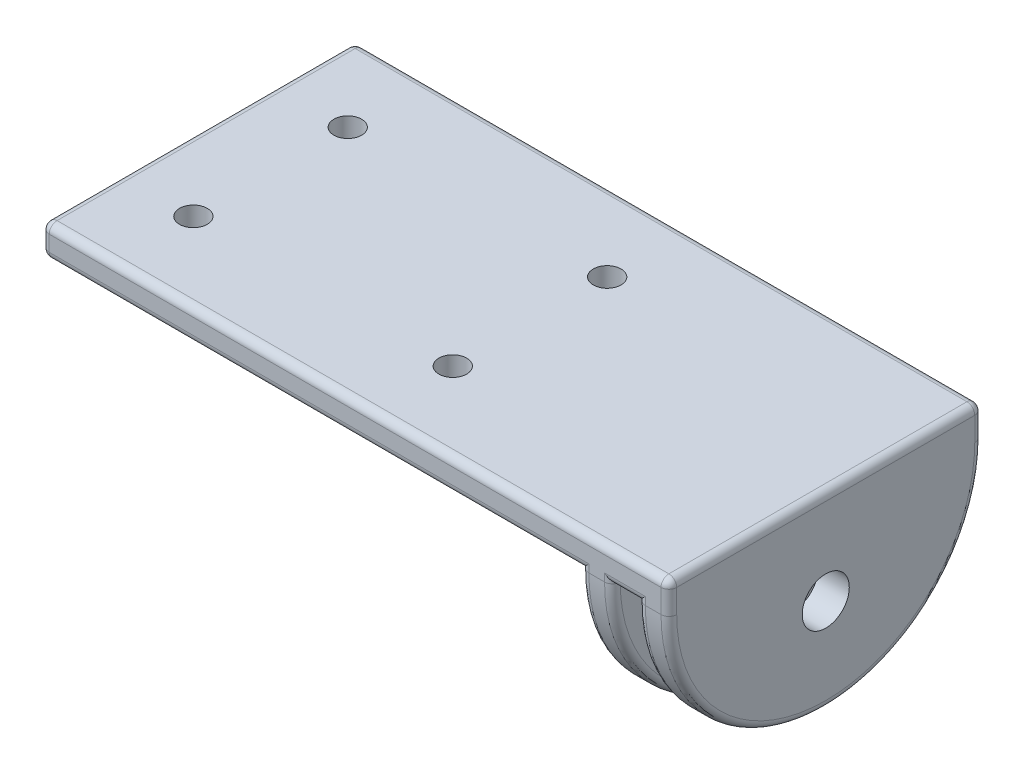
SolidWorks part; units mm, degrees
ref_plane "Front Plane" through (0, 0, 0) normal (0, 0, 1) x (1, 0, 0)
ref_plane "Top Plane" through (0, 0, 0) normal (0, 1, 0) x (1, 0, 0)
ref_plane "Right Plane" through (0, 0, 0) normal (1, 0, 0) x (0, 0, -1)
sketch "Sketch1" plane through (0, 0, 0) normal (0, 1, 0) x (1, 0, 0)
  line L1 (-25.4, -12.7) -> (25.4, -12.7)
  line L2 (-25.4, -12.7) -> (-25.4, 12.7)
  line L3 (-25.4, 12.7) -> (25.4, 12.7)
  line L4 (25.4, -12.7) -> (25.4, 12.7)
  line L5 (-25.4, -12.7) -> (25.4, 12.7) construction
  line L6 (-25.4, 12.7) -> (25.4, -12.7) construction
  point P0 (0, 0)
  dimension "D1" = 50.8
  dimension "D2" = 25.4
extrude "Boss-Extrude1" add sketch "Sketch1" along normal blind 2.54
sketch "Sketch4" plane through (25.4, 0, 0) normal (1, 0, 0) x (0, 0, -1)
  line L0 (-12.7, 0) -> (12.7, 0) construction
  line L1 (-12.7, 2.54) -> (-12.7, 0) construction
  line L2 (12.7, 0) -> (-12.7, 0)
  arc A0 (12.7, 0) -> (-12.7, 0) centre (0, 0) cw
extrude "Boss-Extrude2" add sketch "Sketch4" against normal blind 2.54
pattern_linear "LPattern1" count 2 spacing 4.572 along (-1, 0, 0) of "Boss-Extrude2"
sketch "Sketch5" plane through (25.4, 0, 0) normal (1, 0, 0) x (0, 0, -1)
  line L0 (-12.7, 2.54) -> (12.7, 2.54) construction
  circle A0 centre (0, -5.08) radius 1.905
  dimension "D1" = 3.81
  dimension "D2" = 7.62
extrude "Cut-Extrude1" cut sketch "Sketch5" against normal through all
sketch "Sketch6" plane through (0, 2.54, 0) normal (0, 1, 0) x (1, 0, 0)
  line L0 (-9.0461, 13.0748) -> (-9.0461, -11.9327) construction
  line L1 (0, 0) -> (-30.1304, 0) construction
  circle A0 centre (-19.5461, 6.25) radius 1.125
  circle A1 centre (1.4539, 6.25) radius 1.125
  circle A2 centre (1.4539, -6.25) radius 1.125
  circle A3 centre (-19.5461, -6.25) radius 1.125
  dimension "D1" = 2.25
  dimension "D2" = 21
  dimension "D3" = 12.5
extrude "Cut-Extrude2" cut sketch "Sketch6" against normal through all
fillet "Fillet1" radius 0.635 17 edges at (25.4, -12.7, 0) (-25.4, 2.54, 0) (-25.4, 0, 0) (25.4, 1.27, -12.7) (0, 2.54, -12.7) (-25.4, 1.27, -12.7) (-3.556, 0, -12.7) (21.844, 0, -12.7) (-25.4, 1.27, 12.7) (0, 2.54, 12.7) (25.4, 1.27, 12.7) (21.844, 0, 12.7) (-3.556, 0, 12.7) (25.4, 2.54, 0) (22.86, -12.7, 0) (20.828, -12.7, 0) (18.288, -12.7, 0)
